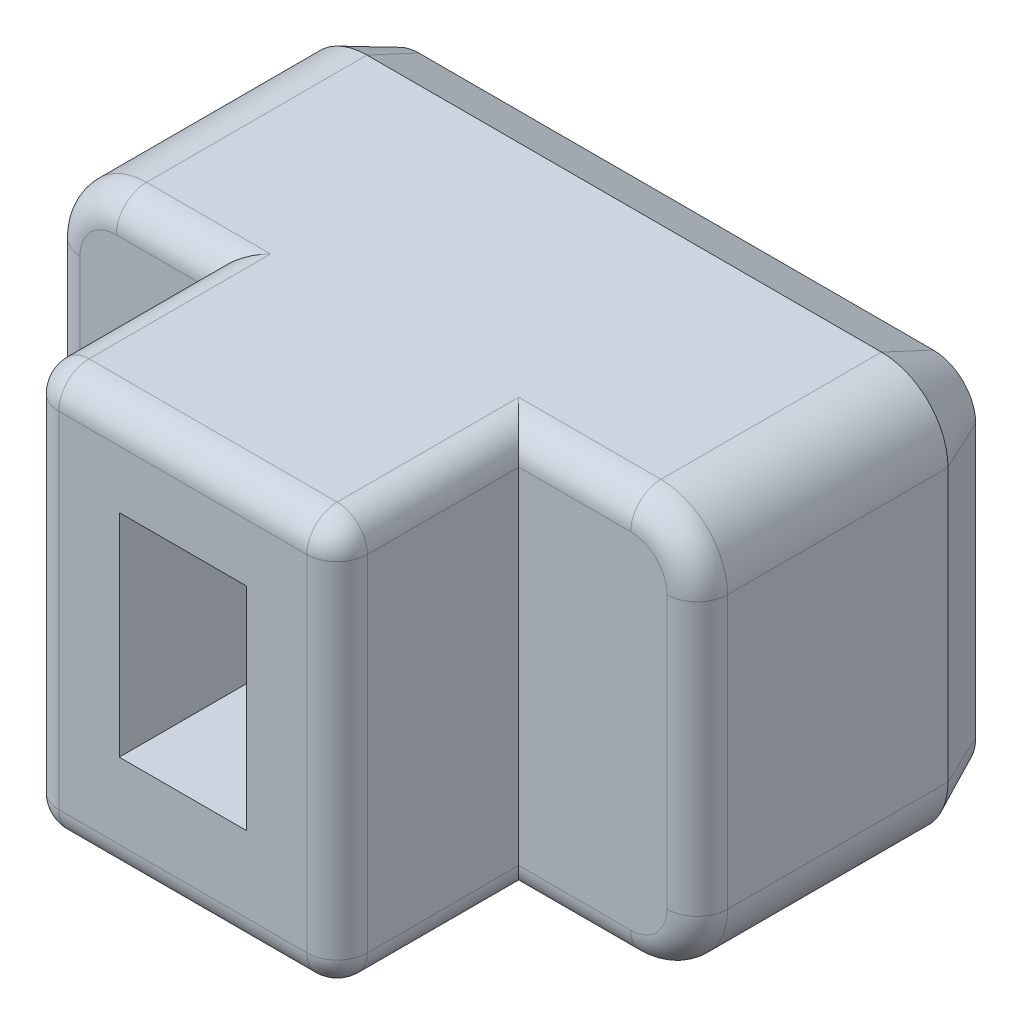
SolidWorks part; units mm, degrees
ref_plane "Plan de face" through (0, 0, 0) normal (0, 0, 1) x (1, 0, 0)
ref_plane "Plan de dessus" through (0, 0, 0) normal (0, 1, 0) x (1, 0, 0)
ref_plane "Plan de droite" through (0, 0, 0) normal (1, 0, 0) x (0, 0, -1)
sketch "Esquisse2" plane through (0, 0, 0) normal (0, 0, 1) x (1, 0, 0)
  line L1 (1.1, 0) -> (9.6, 0)
  line L2 (0, 1.1) -> (0, 5.6)
  line L3 (1.1, 6.7) -> (9.6, 6.7)
  line L4 (10.7, 1.1) -> (10.7, 5.6)
  arc A0 (9.6, 6.7) -> (10.7, 5.6) centre (9.6, 5.6) cw
  arc A1 (9.6, 0) -> (10.7, 1.1) centre (9.6, 1.1) ccw
  arc A2 (1.1, 0) -> (0, 1.1) centre (1.1, 1.1) cw
  arc A3 (0, 5.6) -> (1.1, 6.7) centre (1.1, 5.6) cw
  point P7 (10.7, 6.7)
  point P12 (0, 0)
  point P15 (0, 6.7)
  dimension "D3" = 1.1
  dimension "D1" = 10.7
  dimension "D2" = 6.7
extrude "Boss.-Extru.1" add sketch "Esquisse2" along normal blind 8
sketch "Esquisse3" plane through (0, 0, 8) normal (0, 0, 1) x (1, 0, 0)
  line L0 (0, 5.6) -> (0, 1.1) construction
  line L1 (4.15, 5.25) -> (6.25, 5.25)
  line L2 (4.15, 5.25) -> (4.15, 1.75)
  line L3 (4.15, 1.75) -> (6.25, 1.75)
  line L4 (6.25, 5.25) -> (6.25, 1.75)
  line L5 (10.7, 1.1) -> (10.7, 5.6) construction
  line L6 (9.6, 6.7) -> (1.1, 6.7) construction
  line L7 (1.1, 0) -> (9.6, 0) construction
  dimension "D1" = 2.1
  dimension "D2" = 3.5
  dimension "D3" = 4.15
  dimension "D4" = 4.45
  dimension "D5" = 1.45
  dimension "D6" = 1.75
extrude "Enlèv. mat.-Extru.1" cut sketch "Esquisse3" against normal blind 3
sketch "Esquisse4" plane through (0, 0, 8) normal (0, 0, 1) x (1, 0, 0)
  line L0 (2.65, 6.7) -> (2.65, 0)
  line L1 (9.6, 6.7) -> (1.1, 6.7) construction
  line L2 (1.1, 0) -> (9.6, 0) construction
  line L3 (2.65, 0) -> (7.75, 0)
  line L4 (7.75, 0) -> (7.75, 6.7)
  line L5 (7.75, 6.7) -> (2.65, 6.7)
  line L6 (4.15, 5.25) -> (4.15, 1.75) construction
  line L7 (6.25, 1.75) -> (6.25, 5.25) construction
  dimension "D1" = 1.5
  dimension "D2" = 1.5
extrude "Enlèv. mat.-Extru.2" cut sketch "Esquisse4" against normal blind 3 flip side to cut
fillet "Congé1" radius 0.5 18 edges at (8.675, 0, 5) (10.3778, 0.3222, 5) (10.7, 3.35, 5) (10.3778, 6.3778, 5) (1.875, 6.7, 5) (0.3222, 6.3778, 5) (1.875, 0, 5) (0.3222, 0.3222, 5) (7.75, 6.7, 6.5) (2.65, 6.7, 6.5) (7.75, 0, 6.5) (2.65, 0, 6.5) (2.65, 3.35, 8) (5.2, 6.7, 8) (7.75, 3.35, 8) (5.2, 0, 8) (8.675, 6.7, 5) (0, 3.35, 5)
chamfer "Chanfrein1" distance 0.4 angle 65 8 edges at (5.35, 0, 0) (10.3778, 0.3222, 0) (0.3222, 0.3222, 0) (10.7, 3.35, 0) (0, 3.35, 0) (10.3778, 6.3778, 0) (0.3222, 6.3778, 0) (5.35, 6.7, 0) first distance on face at (5.35, 3.35, 0)
sketch "Esquisse5" plane through (0, 0, 0) normal (0, 0, 1) x (1, 0, 0)
  line L0 (-0.9378, 5.093) -> (11.6517, 5.093) construction
  text T0 "MENU" font "Corbel" height 3.25
extrude "Enlèv. mat.-Extru.3" cut sketch "Esquisse5" along normal blind 0.2
extrude "Boss.-Extru.2" add sketch "Esquisse5<4>" against normal blind 0.2
sketch "Esquisse5<4>" plane through (0, 0, 0) normal (0, 0, 1) x (1, 0, 0) same geometry as "Esquisse5"
